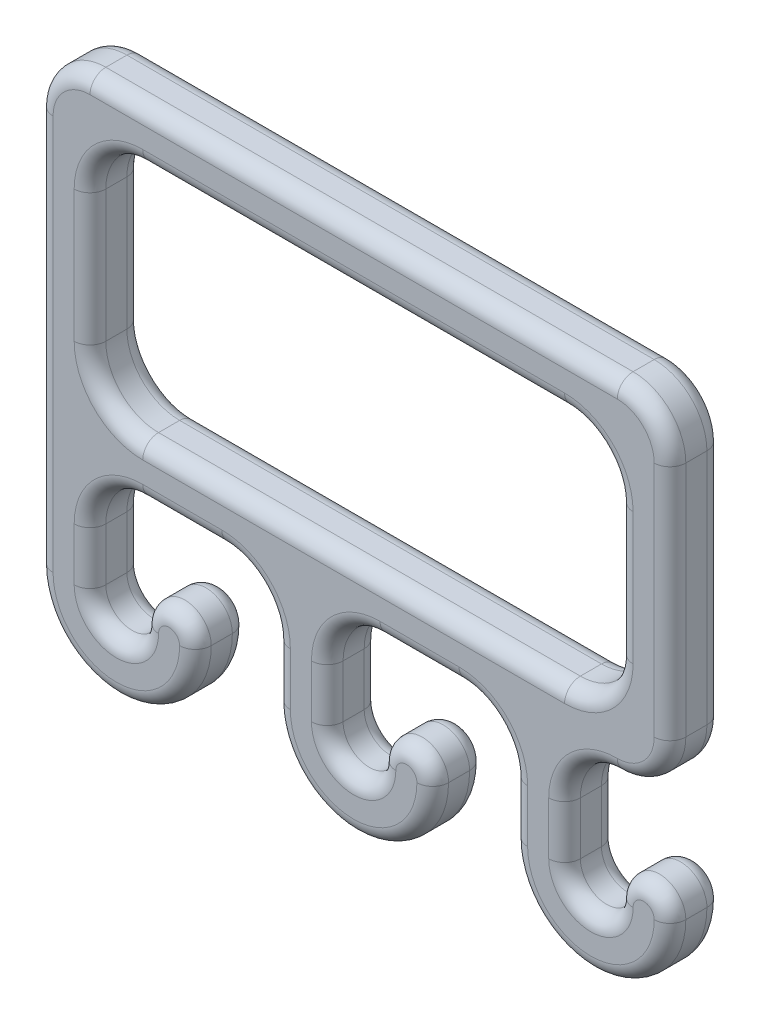
SolidWorks part; units mm, degrees
ref_plane "Plano frontal" through (0, 0, 0) normal (0, 0, 1) x (1, 0, 0)
ref_plane "Plano superior" through (0, 0, 0) normal (0, 1, 0) x (1, 0, 0)
ref_plane "Plano direito" through (0, 0, 0) normal (1, 0, 0) x (0, 0, -1)
sketch "Esboço1" plane through (0, 0, 0) normal (0, 0, 1) x (1, 0, 0)
  line L0 (-10, 55) -> (110, 55)
  line L1 (0, 0) -> (100, 0)
  line L2 (0, 0) -> (0, 45)
  line L3 (0, 45) -> (100, 45)
  line L4 (100, 0) -> (100, 45)
  line L5 (110, -10) -> (110, 55)
  line L6 (-10, -10) -> (110, -10)
  line L7 (-10, -10) -> (-10, 55)
  line B0 (-10, -10) -> (-10, -30)
  line B1 (0, -10) -> (0, -30)
  arc B2 (-10, -30) -> (20, -30) centre (5, -30) ccw
  arc B3 (0, -30) -> (10, -30) centre (5, -30) ccw
  arc B4 (20, -30) -> (10, -30) centre (15, -30) ccw
  line B5 (35, -10) -> (35, -30)
  line B6 (45, -10) -> (45, -30)
  arc B7 (35, -30) -> (65, -30) centre (50, -30) ccw
  arc B8 (45, -30) -> (55, -30) centre (50, -30) ccw
  arc B9 (65, -30) -> (55, -30) centre (60, -30) ccw
  line B10 (80, -10) -> (80, -30)
  line B11 (90, -10) -> (90, -30)
  arc B12 (80, -30) -> (110, -30) centre (95, -30) ccw
  arc B13 (90, -30) -> (100, -30) centre (95, -30) ccw
  arc B14 (110, -30) -> (100, -30) centre (105, -30) ccw
  dimension "D4" = 3
  dimension "D1" = 100
  dimension "D2" = 45
  dimension "D3" = 10
sketch_block_instance "Bloco1-1"
sketch_block "Bloco1"
sketch_block_instance "Bloco1-2"
sketch_block_instance "Bloco1-3"
extrude "Ressalto-extrusão1" add sketch "Esboço1" along normal blind 10 contours L7 L6 L5 L0 L4 L1 L2 L3 | B7 B9 B8 B6 L6 B5 | B12 B14 B13 B11 L6 B10 | B2 B4 B3 B1 L6 B0 region at (50, 53.6353, 0) region at (-5, -10.461, 0) region at (89.539, -20, 0) region at (40, -10.461, 0)
fillet "Filete1" radius 10 12 edges at (100, 45, 5) (100, 0, 5) (0, 0, 5) (0, 45, 5) (35, -10, 5) (80, -10, 5) (90, -10, 5) (45, -10, 5) (0, -10, 5) (110, -10, 5) (110, 55, 5) (-10, 55, 5)
fillet "Filete3" radius 3 70 edges at (-7.0711, 52.0711, 0) (-10, 7.5, 0) (5, -45, 0) (15, -25, 0) (5, -35, 0) (0, -25, 0) (2.9289, -12.9289, 0) (17.5, -10, 0) (32.0711, -12.9289, 0) (35, -25, 0) (50, -45, 0) (60, -25, 0) (50, -35, 0) (45, -25, 0) (47.9289, -12.9289, 0) (62.5, -10, 0) (77.0711, -12.9289, 0) (80, -25, 0) (95, -45, 0) (105, -25, 0) (95, -35, 0) (90, -25, 0) (92.9289, -12.9289, 0) (107.0711, -7.0711, 0) (110, 22.5, 0) (107.0711, 52.0711, 0) (-7.0711, 52.0711, 10) (-10, 7.5, 10) (5, -45, 10) (15, -25, 10) (5, -35, 10) (0, -25, 10) (2.9289, -12.9289, 10) (17.5, -10, 10) (32.0711, -12.9289, 10) (35, -25, 10) (50, -45, 10) (60, -25, 10) (50, -35, 10) (45, -25, 10) (47.9289, -12.9289, 10) (62.5, -10, 10) (77.0711, -12.9289, 10) (80, -25, 10) (95, -45, 10) (105, -25, 10) (95, -35, 10) (90, -25, 10) (92.9289, -12.9289, 10) (107.0711, -7.0711, 10) (110, 22.5, 10) (107.0711, 52.0711, 10) (2.9289, 42.0711, 0) (0, 22.5, 0) (2.9289, 2.9289, 0) (50, 0, 0) (97.0711, 2.9289, 0) (100, 22.5, 0) (97.0711, 42.0711, 0) (2.9289, 42.0711, 10) (0, 22.5, 10) (2.9289, 2.9289, 10) (50, 0, 10) (97.0711, 2.9289, 10) (100, 22.5, 10) (97.0711, 42.0711, 10) (50, 55, 0) (50, 55, 10) (50, 45, 0) (50, 45, 10)
